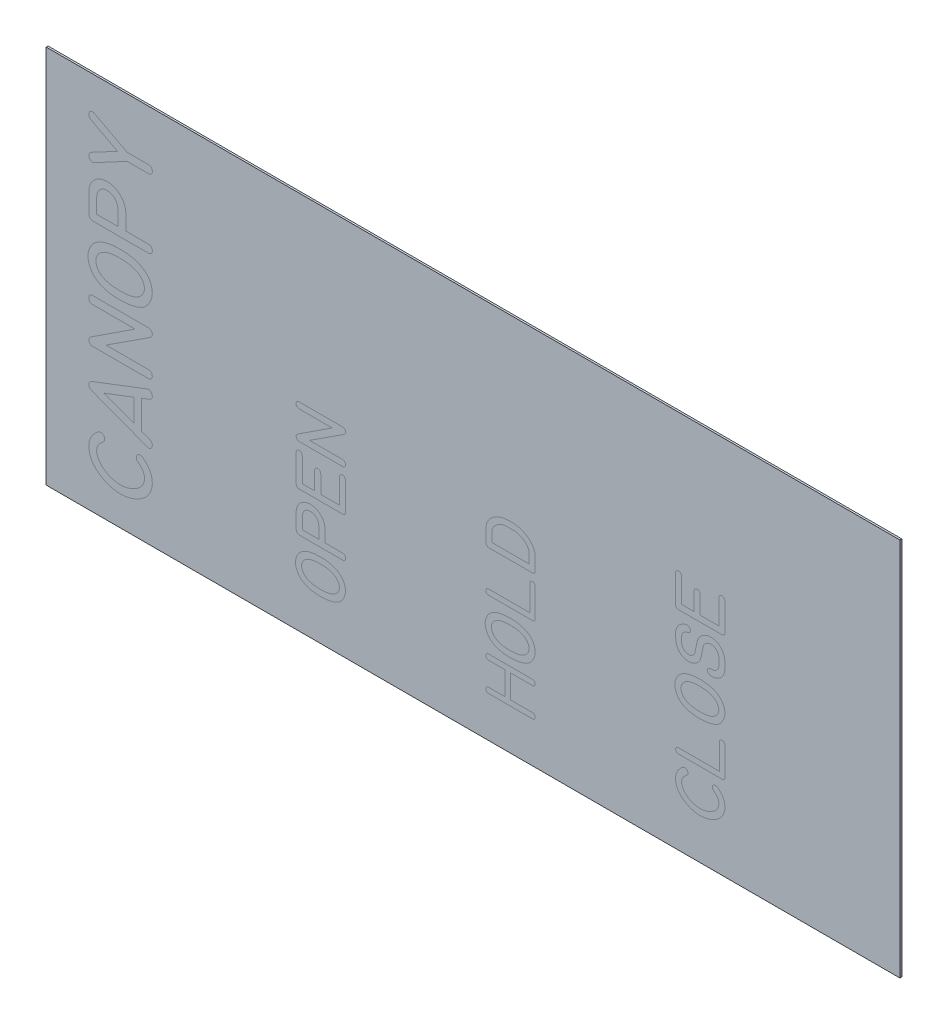
SolidWorks part; units mm, degrees
material "PVC 0.007 Plasticized"
ref_plane "Front" through (0, 0, 0) normal (0, 0, 1) x (1, 0, 0)
ref_plane "Top" through (0, 0, 0) normal (0, 1, 0) x (1, 0, 0)
ref_plane "Right" through (0, 0, 0) normal (1, 0, 0) x (0, 0, -1)
sketch "Sketch1" plane through (0, 0, 0) normal (0, 0, 1) x (1, 0, 0)
  line L0 (-3209.076, 6172.2) -> (-3266.226, 6172.2)
  line L1 (-3273.1086, 6172.2) -> (-3202.1934, 6172.2) construction
  line L2 (-3266.226, 6172.2) -> (-3266.226, 6197.6)
  line L3 (-3266.226, 6197.6) -> (-3209.076, 6197.6)
  line L4 (-3209.076, 6197.6) -> (-3209.076, 6172.2)
  point P5 (-3237.651, 6172.2)
  dimension "D1" = 25.4
  dimension "D2" = 57.15
extrude "Boss-Extrude1" add sketch "Sketch1" along normal blind 0.127
sketch "Sketch2" plane through (0, 0, 0.127) normal (0, 0, 1) x (1, 0, 0)
  line L0 (-3259.1223, 6172.2) -> (-3259.1223, 6197.6) construction
  line L1 (-3266.226, 6172.2) -> (-3209.076, 6172.2) construction
  line L2 (-3209.076, 6197.6) -> (-3266.226, 6197.6) construction
  line L3 (-3266.226, 6174.74) -> (-3209.076, 6174.74) construction
  line L4 (-3266.226, 6197.6) -> (-3266.226, 6172.2) construction
  line L5 (-3209.076, 6172.2) -> (-3209.076, 6197.6) construction
  line L6 (-3246.1862, 6174.74) -> (-3246.1862, 6197.6) construction
  line L7 (-3233.4862, 6174.74) -> (-3233.4862, 6197.6) construction
  line L8 (-3220.7862, 6174.74) -> (-3220.7862, 6197.6) construction
  line L10 (-3241.4872, 6176.9625) -> (-3228.7872, 6176.9625) construction
  line L11 (-3241.4872, 6178.55) -> (-3241.4872, 6175.375) construction
  line L12 (-3228.7872, 6175.375) -> (-3228.7872, 6178.55) construction
  text T0 "CANOPY" font "GordonURWMed" height in points 18
  text T1 "OPEN" font "GordonURWMed" height in points 14
  text T2 "HOLD" font "GordonURWMed" height in points 14
  text T3 "CLOSE" font "GordonURWMed" height in points 14
  point P25 (-3235.1372, 6176.9625)
  dimension "D1" = 2.54
  dimension "D2" = 1.651
  dimension "D3" = 11.049
  dimension "D4" = 14.351
wrap "Wrap1" sketch "Sketch2" wrap type scribe source sketch "Sketch2" face at (-3237.651, 6184.9, 0.127)
